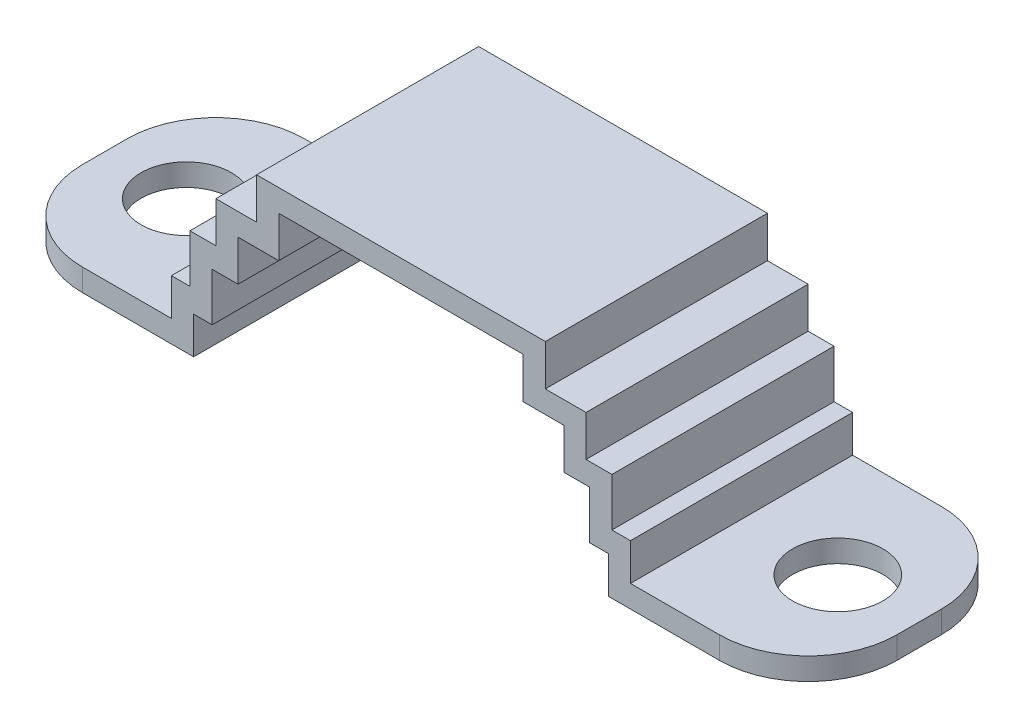
SolidWorks part; units mm, degrees
ref_plane "Front Plane" through (0, 0, 0) normal (0, 0, 1) x (1, 0, 0)
ref_plane "Top Plane" through (0, 0, 0) normal (0, 1, 0) x (1, 0, 0)
ref_plane "Right Plane" through (0, 0, 0) normal (1, 0, 0) x (0, 0, -1)
sketch "Sketch1" plane through (0, 0, 0) normal (0, 0, 1) x (1, 0, 0)
  line L0 (-55, 4.5) -> (-28, 4.5)
  line L1 (-28, 4.5) -> (-28, 9.5)
  line L2 (-28, 9.5) -> (-25.5, 9.5)
  line L3 (-25.5, 9.5) -> (-25.5, 16)
  line L4 (-25.5, 16) -> (-22, 16)
  line L5 (-22, 16) -> (-22, 21.5)
  line L6 (-22, 21.5) -> (-16.5, 21.5)
  line L7 (-16.5, 21.5) -> (-16.5, 27.05)
  line L8 (-16.5, 27.05) -> (0, 27.05)
  circle A0 centre (0, 0) radius 27.05
  dimension "D1" = 54.1
  dimension "D2" = 27
  dimension "D3" = 4.5
  dimension "D4" = 28
  dimension "D5" = 5
  dimension "D6" = 2.5
  dimension "D7" = 6.5
  dimension "D8" = 3.5
  dimension "D9" = 5.5
  dimension "D10" = 5.5
  dimension "D11" = 16.5
  dimension "D12" = 5.55
extrude "Extrude-Thin1" add sketch "Sketch1" along normal mid plane 30 thin contours L0 L1 L2 L3 L4 L5 L6 L7 L8 thin type one direction reverse wall 3
sketch "Sketch2" plane through (0, 7.5, 0) normal (0, 1, 0) x (1, 0, 0)
  line L0 (0, -15) -> (0, 15) construction
  circle A0 centre (-44, 0) radius 6.1
  dimension "D1" = 12.2
  dimension "D2" = 44
extrude "Cut-Extrude1" cut sketch "Sketch2" against normal through all
fillet "Fillet1" radius 12 2 edges at (-55, 6, -15) (-55, 6, 15)
mirror "Mirror1" about plane through (0, 30.05, 15) normal (1, 0, 0) of "Fillet1", "Cut-Extrude1", "Extrude-Thin1"
